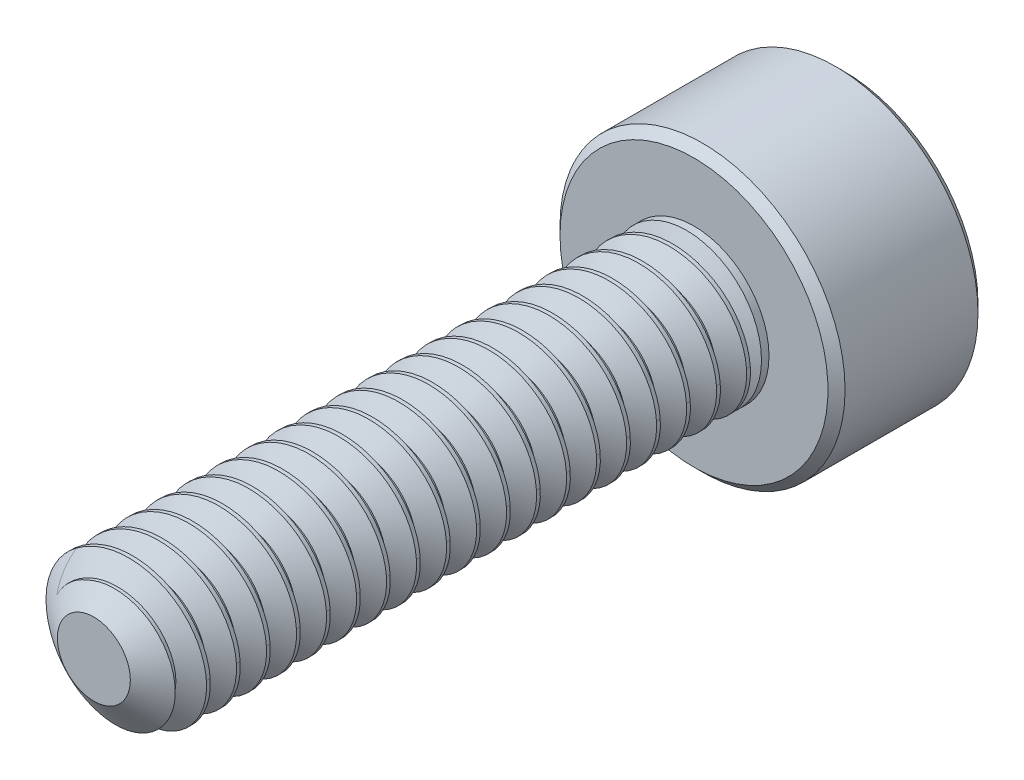
SolidWorks part; units mm, degrees
ref_plane "Front Plane" through (0, 0, 0) normal (0, 0, 1) x (1, 0, 0)
ref_plane "Top Plane" through (0, 0, 0) normal (0, 1, 0) x (1, 0, 0)
ref_plane "Right Plane" through (0, 0, 0) normal (1, 0, 0) x (0, 0, -1)
sketch "Sketch1" plane through (0, 0, 0) normal (0, 0, 1) x (1, 0, 0)
  circle A0 centre (0, 0) radius 1
  dimension "OD" = 2
extrude "Extrude1" add sketch "Sketch1" against normal blind 8
sketch "Sketch2" plane through (0, 0, 0) normal (0, 0, 1) x (1, 0, 0)
  circle A0 centre (0, 0) radius 1 construction
  circle A1 centre (0, 0) radius 1
curve "Helix/Spiral1" pitch 0.4 height 8.4 turns 21 parameters "pitch"=0.4
sketch "Sketch3" plane through (0, 0, 0) normal (1, 0, 0) x (0, 0, -1)
  line L0 (-0.35, 1) -> (-0.2, 0.7402)
  line L1 (-0.2, 0.7402) -> (-0.15, 0.7402)
  line L2 (-0.15, 0.7402) -> (0, 1)
  line L3 (-0.35, 1) -> (0, 1)
  line L4 (-0.175, 1) -> (-0.175, 0.7402) construction
  line L5 (-0.275, 0.8701) -> (-0.075, 0.8701) construction
  line L6 (0, 1) -> (0, -1) construction
  line L7 (0, -1) -> (8, -1) construction
  point P11 (1.8, -1)
  dimension "D1" = 0.05
  dimension "D2" = 0.2
  dimension "D3" = 60
  dimension "D4" = 1.8
sweep "Cut-Sweep1" cut profiles "Sketch3" path "Helix/Spiral1" align with end faces yes
sketch "Sketch4" plane through (0, 0, 0) normal (1, 0, 0) x (0, 0, -1)
  line L0 (0.3598, 1) -> (0, 0.4862)
  line L1 (0, 0.4862) -> (0, 1)
  line L2 (0.3598, 1) -> (0, 1)
  line L3 (-0.35, 1) -> (0, 1) construction
  line L4 (0, 0) -> (7.0209, 0) construction
  dimension "D1" = 55
  dimension "D2" = 0.254
revolve "Cut-Revolve1" cut sketch "Sketch4" angle 360 about L4
sketch "Sketch5" plane through (0, 0, 0) normal (1, 0, 0) x (0, 0, -1)
  line L0 (8, -0.7473) -> (8, 0.7135) construction
  line L1 (8, 1) -> (0.1203, 1)
  line L2 (8, 1) -> (8, 0)
  line L3 (8, 0) -> (0.0001, 0)
  line L4 (0.0001, 0.6698) -> (0.0001, 0)
  line L5 (0.1203, 1) -> (0.0001, 0.6698)
  line L6 (0, 0) -> (9.9695, 0) construction
  point P3 (0.0001, 1)
  point P10 (0.0001, 1)
  dimension "D1" = 0.3302
  dimension "Thread min" = 0.0001
  dimension "D3" = 20
revolve "partially thread" [suppressed] add sketch "Sketch5" angle 360 about L6
sketch "Sketch6" plane through (0, 0, -8) normal (0, 0, -1) x (-1, 0, 0)
  circle A0 centre (0, 0) radius 1.9
  dimension "head dia" = 3.8
extrude "Extrude2" add sketch "Sketch6" along normal blind 2
sketch "Sketch7" plane through (0, 0, -10) normal (0, 0, -1) x (-1, 0, 0)
  line L1 (0, 0.866) -> (-0.75, 0.433)
  line L2 (-0.75, 0.433) -> (-0.75, -0.433)
  line L3 (-0.75, -0.433) -> (0, -0.866)
  line L4 (0, -0.866) -> (0.75, -0.433)
  line L5 (0.75, -0.433) -> (0.75, 0.433)
  line L6 (0.75, 0.433) -> (0, 0.866)
  circle A0 centre (0, 0) radius 0.75 construction
  dimension "hex dia" = 1.5
extrude "Cut-Extrude1" cut sketch "Sketch7" against normal blind 1.125
sketch "Sketch8" plane through (0, 0, -10) normal (0, 0, -1) x (-1, 0, 0)
  circle A0 centre (0, 0) radius 0.866
extrude "Cut-Extrude2" cut sketch "Sketch8" against normal through all draft 45
chamfer "Chamfer1" distance 0.114 angle 45 2 edges at (-1.9, 0, -10) (-1.9, 0, -8)
sketch "Sketch9" plane through (0, 0, 0) normal (1, 0, 0) x (0, 0, -1)
  line L0 (0, 1) -> (0, -1) construction
  line L1 (2.2, 1) -> (2.2, -1) construction
  dimension "D1" = 2.2
sketch "Sketch10" plane through (0, 0, 0) normal (1, 0, 0) x (0, 0, -1)
  line L0 (8, 1) -> (8, 0)
  line L1 (8, 1) -> (7.9, 1)
  line L2 (7.9, 1) -> (7.4858, 0)
  line L3 (8, 0) -> (7.4858, 0)
  line L4 (8, 1.786) -> (8, -1.786) construction
  dimension "D1" = 22.5
  dimension "D2" = 0.1
revolve "Revolve1" add sketch "Sketch10" angle 360 about L3
equation "\"D3@Helix/Spiral1\" = \"screw length@Extrude1\"+\"pitch@Helix/Spiral1\""
equation "\"D1@Sketch3\" = \"pitch@Helix/Spiral1\"*.125"
equation "\"D2@Sketch3\" = \"pitch@Helix/Spiral1\"*.5"
equation "\"D1@Cut-Extrude1\" = \"hex dia@Sketch7\"*.75"
equation "\"D1@Chamfer1\" = \"head dia@Sketch6\"*.03"
equation "\"D1@Sketch9\" = \"pitch@Helix/Spiral1\"*5.5"
equation "\"D2@Sketch10\" = \"pitch@Helix/Spiral1\"*.25"
equation "\"D4@Sketch3\" = \"pitch@Helix/Spiral1\"*4.50"
